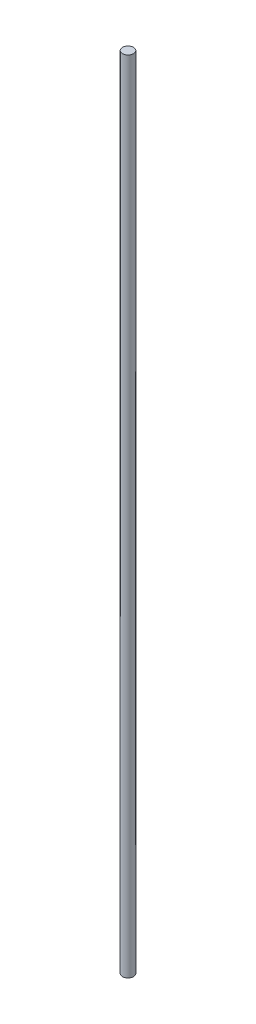
SolidWorks part; units mm, degrees
material "Plain Carbon Steel"
ref_plane "Front Plane" through (0, 0, 0) normal (0, 0, 1) x (1, 0, 0)
ref_plane "Top Plane" through (0, 0, 0) normal (0, 1, 0) x (1, 0, 0)
ref_plane "Right Plane" through (0, 0, 0) normal (1, 0, 0) x (0, 0, -1)
sketch "Sketch1" plane through (0, 0, 0) normal (0, 1, 0) x (1, 0, 0)
  circle A0 centre (0, 0) radius 1
  dimension "D1" = 2
extrude "Boss-Extrude1" add sketch "Sketch1" along normal blind 145.3
